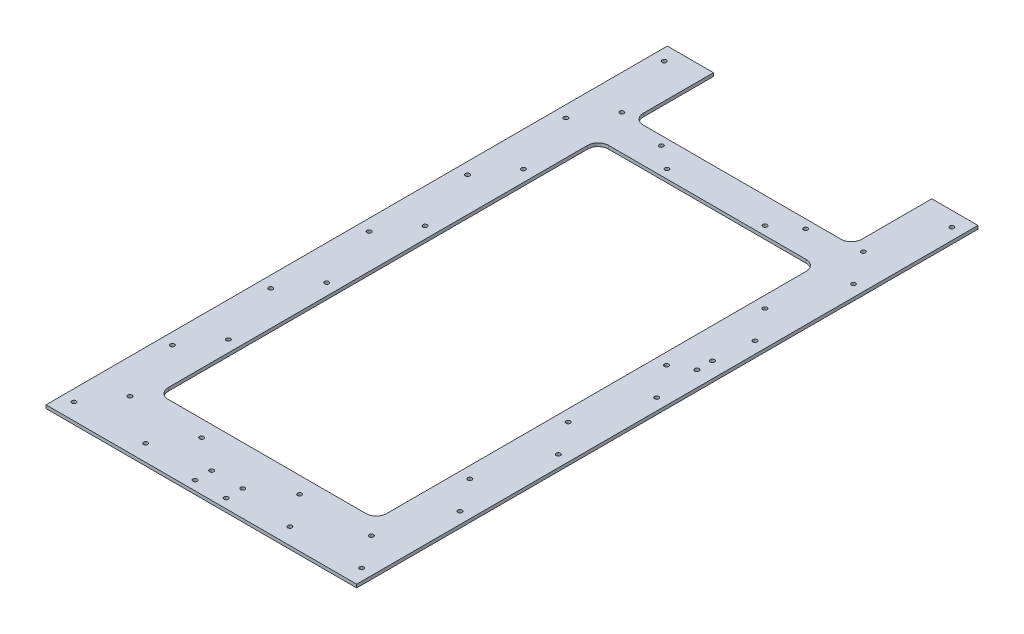
SolidWorks part; units mm, degrees
ref_plane "Front Plane" through (0, 0, 0) normal (0, 0, 1) x (1, 0, 0)
ref_plane "Top Plane" through (0, 0, 0) normal (0, 1, 0) x (1, 0, 0)
ref_plane "Right Plane" through (0, 0, 0) normal (1, 0, 0) x (0, 0, -1)
sketch "Sketch1" plane through (0, 0, 0) normal (0, 1, 0) x (1, 0, 0)
  line L1 (150, -300) -> (-150, -300)
  line L2 (150, -300) -> (150, 300)
  line L3 (150, 300) -> (-150, 300)
  line L4 (-150, -300) -> (-150, 300)
  line L5 (150, -300) -> (-150, 300) construction
  line L6 (150, 300) -> (-150, -300) construction
  point P0 (0, 0)
  dimension "D1" = 600
  dimension "D2" = 300
extrude "Boss-Extrude1" add sketch "Sketch1" along normal blind 3.175
sketch "Sketch3" plane through (0, 3.175, 0) normal (0, 1, 0) x (1, 0, 0)
  line L0 (-95.4457, -236.4845) -> (95.4457, -236.4845)
  line L1 (0, 300) -> (0, -300) construction
  line L2 (105.4457, -226.4845) -> (105.4457, 178.5785)
  line L3 (95.4457, 188.5785) -> (-95.4457, 188.5785)
  line L4 (105.4457, 338.7705) -> (105.4457, 232.3181)
  line L5 (150, 300) -> (-150, 300) construction
  line L6 (95.4457, 222.3181) -> (-95.4457, 222.3181)
  line L7 (95.4457, 348.7705) -> (-95.4457, 348.7705)
  line L8 (0, -300) -> (0, -342.0806) construction
  line L9 (-105.4457, 338.7705) -> (-105.4457, 232.3181)
  line L10 (-105.4457, -226.4845) -> (-105.4457, 178.5785)
  arc A0 (-105.4457, 338.7705) -> (-95.4457, 348.7705) centre (-95.4457, 338.7705) cw
  arc A1 (-105.4457, 232.3181) -> (-95.4457, 222.3181) centre (-95.4457, 232.3181) ccw
  arc A2 (105.4457, 338.7705) -> (95.4457, 348.7705) centre (95.4457, 338.7705) ccw
  arc A3 (105.4457, 232.3181) -> (95.4457, 222.3181) centre (95.4457, 232.3181) cw
  arc A4 (105.4457, 178.5785) -> (95.4457, 188.5785) centre (95.4457, 178.5785) ccw
  arc A5 (-105.4457, 178.5785) -> (-95.4457, 188.5785) centre (-95.4457, 178.5785) cw
  arc A6 (-105.4457, -226.4845) -> (-95.4457, -236.4845) centre (-95.4457, -226.4845) ccw
  arc A7 (95.4457, -236.4845) -> (105.4457, -226.4845) centre (95.4457, -226.4845) ccw
  point P17 (0, 300)
  point P18 (0, 222.3181)
  point P19 (0, 188.5785)
  point P20 (0, -236.4845)
  point P22 (-105.4457, 300)
  point P25 (-105.4457, 222.3181)
  point P28 (105.4457, 300)
  point P31 (105.4457, 222.3181)
  point P34 (105.4457, 188.5785)
  point P37 (-105.4457, 188.5785)
  point P40 (-105.4457, -236.4845)
  point P43 (105.4457, -236.4845)
  dimension "D1" = 10
extrude "Cut-Extrude1" cut sketch "Sketch3" against normal blind 10
sketch "Sketch4" plane through (0, 3.175, 0) normal (0, 1, 0) x (1, 0, 0)
  circle A0 centre (15, -291) radius 2.05
  circle A1 centre (-15, -291) radius 2.05
  circle A2 centre (-15, -275) radius 2.05
  circle A3 centre (15, -275) radius 2.05
  dimension "D1" = 4.1
extrude "Cut-Extrude2" cut sketch "Sketch4" against normal blind 51
sketch "Sketch5" plane through (0, 3.175, 0) normal (0, 1, 0) x (1, 0, 0)
  circle A0 centre (135, 43.495) radius 2.1
  circle A1 centre (135, 58.495) radius 2.1
  dimension "D1" = 4.2
extrude "Cut-Extrude3" cut sketch "Sketch5" against normal blind 67
sketch "Sketch7" plane through (0, 3.175, 0) normal (0, 1, 0) x (1, 0, 0)
  line L0 (138.8614, -300) -> (138.8614, 300) construction
  line L1 (116.5842, -300) -> (116.5842, 300) construction
  line L2 (150, -187.519) -> (138.8614, -187.519) construction
  line L3 (150, -300) -> (150, 300) construction
  line L4 (138.8614, -187.519) -> (127.7228, -187.519) construction
  line L5 (127.7228, -187.519) -> (116.5842, -187.519) construction
  line L6 (116.5842, -187.519) -> (105.4457, -187.519) construction
  line L7 (105.4457, -226.4845) -> (105.4457, 178.5785) construction
  line L8 (-150, -300) -> (150, -300) construction
  line L9 (150, 300) -> (105.4457, 300) construction
  line L10 (150, 197.0134) -> (0, 197.0134) construction
  line L12 (150, 213.8832) -> (0, 213.8832) construction
  line L13 (33.148, 222.3181) -> (33.148, 213.8832) construction
  line L14 (-95.4457, 222.3181) -> (95.4457, 222.3181) construction
  line L15 (33.148, 213.8832) -> (33.148, 205.4483) construction
  line L16 (33.148, 205.4483) -> (33.148, 197.0134) construction
  line L17 (33.148, 197.0134) -> (33.148, 188.5785) construction
  line L18 (95.4457, 188.5785) -> (-95.4457, 188.5785) construction
  line L19 (150, -284.1211) -> (0, -284.1211) construction
  line L20 (150, -252.3634) -> (0, -252.3634) construction
  line L21 (55.7313, -236.4845) -> (55.7313, -252.3634) construction
  line L22 (-95.4457, -236.4845) -> (95.4457, -236.4845) construction
  line L23 (55.7313, -252.3634) -> (55.7313, -268.2422) construction
  line L24 (55.7313, -268.2422) -> (55.7313, -284.1211) construction
  line L25 (55.7313, -284.1211) -> (55.7313, -300) construction
  line L26 (-42.5408, 188.5785) -> (-42.5408, -236.4845) construction
  line L27 (0, -284.1211) -> (0, -389.9124) construction
  circle A0 centre (138.8614, -284.1211) radius 2.05
  circle A1 centre (116.5842, -252.3634) radius 2.05
  circle A2 centre (47.3578, -252.3634) radius 2.05
  circle A3 centre (69.635, -284.1211) radius 2.05
  circle A4 centre (116.5842, -157.3634) radius 2.05
  circle A5 centre (138.8614, -189.1211) radius 2.05
  circle A6 centre (116.5842, -62.3634) radius 2.05
  circle A7 centre (138.8614, -94.1211) radius 2.05
  circle A8 centre (116.5842, 32.6366) radius 2.05
  circle A9 centre (138.8614, 0.8789) radius 2.05
  circle A10 centre (116.5842, 127.6366) radius 2.05
  circle A11 centre (138.8614, 95.8789) radius 2.05
  circle A12 centre (116.5842, 222.6366) radius 2.05
  circle A13 centre (138.8614, 190.8789) radius 2.05
  circle A14 centre (116.5842, 317.6366) radius 2.05
  circle A15 centre (138.8614, 285.8789) radius 2.05
  circle A16 centre (47.3578, 197.0134) radius 2.05
  circle A17 centre (69.635, 213.8832) radius 2.05
  circle A18 centre (-47.3578, 197.0134) radius 2.05
  circle A19 centre (-69.635, 213.8832) radius 2.05
  circle A20 centre (-138.8614, 285.8789) radius 2.05
  circle A21 centre (-116.5842, 222.6366) radius 2.05
  circle A22 centre (-138.8614, 190.8789) radius 2.05
  circle A23 centre (-138.8614, 95.8789) radius 2.05
  circle A24 centre (-116.5842, 32.6366) radius 2.05
  circle A25 centre (-116.5842, 127.6366) radius 2.05
  circle A26 centre (-116.5842, -62.3634) radius 2.05
  circle A27 centre (-138.8614, 0.8789) radius 2.05
  circle A28 centre (-138.8614, -94.1211) radius 2.05
  circle A29 centre (-116.5842, -157.3634) radius 2.05
  circle A30 centre (-138.8614, -189.1211) radius 2.05
  circle A31 centre (-116.5842, -252.3634) radius 2.05
  circle A32 centre (-138.8614, -284.1211) radius 2.05
  circle A33 centre (-47.3578, -252.3634) radius 2.05
  circle A34 centre (-69.635, -284.1211) radius 2.05
  dimension "D1" = 4.1
  dimension "D2" = 4.1
  dimension "D3" = 2
  dimension "D4" = 7
extrude "Cut-Extrude4" cut sketch "Sketch7" against normal blind 10
equation "\"D2@Sketch7\"=\"D1@Sketch7\""
